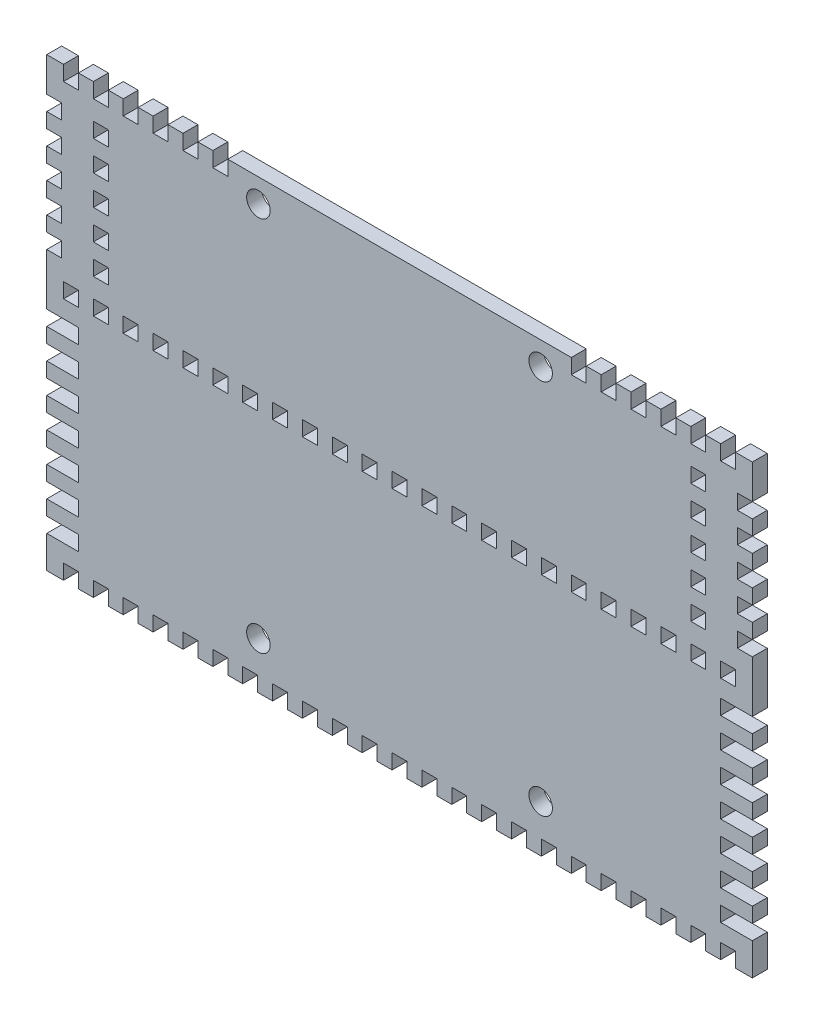
SolidWorks part; units mm, degrees
ref_plane "Front Plane" through (0, 0, 0) normal (0, 0, 1) x (1, 0, 0)
ref_plane "Top Plane" through (0, 0, 0) normal (0, 1, 0) x (1, 0, 0)
ref_plane "Right Plane" through (0, 0, 0) normal (1, 0, 0) x (0, 0, -1)
sketch "Sketch1" plane through (0, 0, 0) normal (0, 0, 1) x (1, 0, 0)
  line L1 (75, -27.5) -> (-75, -27.5)
  line L2 (75, -27.5) -> (75, 27.5)
  line L3 (75, 27.5) -> (-75, 27.5)
  line L4 (-75, -27.5) -> (-75, 27.5)
  line L5 (75, -27.5) -> (-75, 27.5) construction
  line L6 (75, 27.5) -> (-75, -27.5) construction
  point P0 (0, 0)
  dimension "D1" = 150
  dimension "D2" = 55
extrude "Boss-Extrude1" add sketch "Sketch1" along normal blind 3.175
sketch "Sketch2" plane through (0, 0, 0) normal (0, 0, -1) x (-1, 0, 0)
  line L0 (-75, 27.5) -> (75, 27.5) construction
  line L1 (-1.5875, 30.675) -> (1.5875, 30.675)
  line L2 (-1.5875, 30.675) -> (-1.5875, 24.325)
  line L3 (-1.5875, 24.325) -> (1.5875, 24.325)
  line L4 (1.5875, 30.675) -> (1.5875, 24.325)
  line L5 (-1.5875, 30.675) -> (1.5875, 24.325) construction
  line L6 (-1.5875, 24.325) -> (1.5875, 30.675) construction
  point P0 (0, 27.5)
  dimension "D1" = 3.175
  dimension "D2" = 6.35
extrude "Cut-Extrude1" cut sketch "Sketch2" against normal up to next
pattern_linear "LPattern1" count 12 spacing 6.35 along (1, 0, 0) count 12 spacing 6.35 along (-1, 0, 0) of "Cut-Extrude1" pattern seed only yes
mirror "Mirror1" about plane through (0, 0, 0) normal (0, 1, 0) of "LPattern1"
sketch "Sketch3" plane through (0, 0, 0) normal (0, 0, -1) x (-1, 0, 0)
  line L0 (-75, -27.5) -> (-75, 27.5) construction
  line L1 (-78.175, 1.5875) -> (-71.825, 1.5875)
  line L2 (-78.175, 1.5875) -> (-78.175, -1.5875)
  line L3 (-78.175, -1.5875) -> (-71.825, -1.5875)
  line L4 (-71.825, 1.5875) -> (-71.825, -1.5875)
  line L5 (-78.175, 1.5875) -> (-71.825, -1.5875) construction
  line L6 (-78.175, -1.5875) -> (-71.825, 1.5875) construction
  point P0 (-75, 0)
  dimension "D1" = 3.175
  dimension "D2" = 6.35
extrude "Cut-Extrude2" cut sketch "Sketch3" against normal blind 10
pattern_linear "LPattern2" count 4 spacing 6.35 along (0, 1, 0) count 4 spacing 6.35 along (0, -1, 0) of "Cut-Extrude2" pattern seed only yes
mirror "Mirror2" about plane through (0, 0, 0) normal (1, 0, 0) of "LPattern2"
sketch "Sketch4" plane through (0, 0, 0) normal (0, 0, -1) x (-1, 0, 0)
  line L0 (-45, 0) -> (-25, 0) construction
  line L1 (-45, 1.5) -> (-25, 1.5)
  line L2 (-45, -1.5) -> (-25, -1.5)
  line L3 (25, 0) -> (45, 0) construction
  line L4 (25, 1.5) -> (45, 1.5)
  line L5 (25, -1.5) -> (45, -1.5)
  arc A0 (-45, 1.5) -> (-45, -1.5) centre (-45, 0) ccw
  arc A1 (-25, -1.5) -> (-25, 1.5) centre (-25, 0) ccw
  arc A2 (25, 1.5) -> (25, -1.5) centre (25, 0) ccw
  arc A3 (45, -1.5) -> (45, 1.5) centre (45, 0) ccw
  point P2 (-35, 0)
  point P9 (35, 0)
  dimension "D1" = 35
  dimension "D2" = 35
  dimension "D3" = 3
  dimension "D4" = 3
  dimension "D5" = 20
  dimension "D6" = 20
extrude "Cut-Extrude3" [suppressed] cut sketch "Sketch4" against normal blind 10
sketch "Sketch5" plane through (0, 0, 0) normal (0, 0, -1) x (-1, 0, 0)
  line L1 (-75, 27.5) -> (75, 27.5)
  line L2 (-75, 27.5) -> (-75, 67.5)
  line L3 (-75, 67.5) -> (75, 67.5)
  line L4 (75, 27.5) -> (75, 67.5)
  dimension "D1" = 40
extrude "Boss-Extrude2" add sketch "Sketch5" against normal up to surface (3.175 mm away) up to face at (0, 0, 3.175)
sketch "Sketch6" plane through (0, 0, 0) normal (0, 0, -1) x (-1, 0, 0)
  line L0 (-35, 44.0688) -> (35, 44.0688) construction
  line L1 (-25, 44.0687) -> (-45, 44.0687) construction
  line L2 (-25, 42.5688) -> (-45, 42.5688)
  line L3 (-25, 45.5688) -> (-45, 45.5688)
  line L4 (25, 44.0687) -> (45, 44.0688) construction
  line L5 (25, 45.5688) -> (45, 45.5688)
  line L6 (25, 42.5687) -> (45, 42.5688)
  arc A0 (-25, 42.5688) -> (-25, 45.5688) centre (-25, 44.0687) ccw
  arc A1 (-45, 45.5688) -> (-45, 42.5688) centre (-45, 44.0687) ccw
  arc A2 (25, 45.5688) -> (25, 42.5687) centre (25, 44.0687) ccw
  arc A3 (45, 42.5688) -> (45, 45.5688) centre (45, 44.0688) ccw
  point P3 (0, 44.0688)
  point P6 (-35, 44.0688)
  point P12 (35, 44.0688)
  dimension "D1" = 70
  dimension "D2" = 3
  dimension "D3" = 3
  dimension "D4" = 20
  dimension "D5" = 20
extrude "Cut-Extrude4" [suppressed] cut sketch "Sketch6" against normal blind 10
sketch "Sketch7" plane through (0, 0, 0) normal (0, 0, -1) x (-1, 0, 0)
  line L0 (75, 67.5) -> (-75, 67.5) construction
  line L1 (0, 67.5) -> (1.5875, 67.5)
  line L3 (0, 64.325) -> (1.5875, 64.325)
  line L4 (1.5875, 67.5) -> (1.5875, 64.325)
  line L6 (0, 64.325) -> (-1.5875, 64.325)
  line L8 (0, 67.5) -> (-1.5875, 67.5)
  line L9 (-1.5875, 64.325) -> (-1.5875, 67.5)
  dimension "D1" = 1.5875
  dimension "D2" = 3.175
  dimension "D3" = 1.5875
extrude "Cut-Extrude5" cut sketch "Sketch7" against normal blind 10
pattern_linear "LPattern3" count 12 spacing 6.35 along (1, 0, 0) count 12 spacing 6.35 along (-1, 0, 0) of "Cut-Extrude5" pattern seed only yes
sketch "Sketch8" plane through (0, 0, 0) normal (0, 0, -1) x (-1, 0, 0)
  line L0 (-68.2625, 24.325) -> (-68.2625, 27.5) construction
  line L1 (-71.825, 20.6375) -> (-68.2625, 20.6375)
  line L2 (-71.825, 20.6375) -> (-71.825, 17.4625)
  line L3 (-71.825, 17.4625) -> (-68.2625, 17.4625)
  line L4 (-68.2625, 20.6375) -> (-68.2625, 17.4625)
extrude "Cut-Extrude6" cut sketch "Sketch8" against normal blind 10
pattern_linear "LPattern4" count 7 spacing 6.35 along (0, -1, 0) of "Cut-Extrude6"
mirror "Mirror3" about plane through (0, 0, 0) normal (1, 0, 0) of "LPattern4"
sketch "Sketch9" plane through (0, 0, 0) normal (0, 0, -1) x (-1, 0, 0)
  line L1 (-30, 62.5) -> (30, 62.5) construction
  line L2 (-30, 62.5) -> (-30, -17.5) construction
  line L3 (-30, -17.5) -> (30, -17.5) construction
  line L4 (30, 62.5) -> (30, -17.5) construction
  line L5 (-30, 62.5) -> (30, -17.5) construction
  line L6 (-30, -17.5) -> (30, 62.5) construction
  line L7 (-39.6875, -27.5) -> (-42.8625, -27.5) construction
  point P0 (0, 22.5)
  dimension "D1" = 60
  dimension "D2" = 80
  dimension "D3" = 50
sketch "Sketch11" plane through (0, 0, 0) normal (0, 0, -1) x (-1, 0, 0)
  line L1 (-36.5125, 67.5) -> (36.5125, 67.5)
  line L2 (-36.5125, 67.5) -> (-36.5125, 64.325)
  line L3 (-36.5125, 64.325) -> (36.5125, 64.325)
  line L4 (36.5125, 67.5) -> (36.5125, 64.325)
extrude "Boss-Extrude3" add sketch "Sketch11" against normal up to surface (3.175 mm away) up to face at (-19.05, 25.9125, 3.175)
sketch "Sketch10" plane through (0, 0, 0) normal (0, 0, -1) x (-1, 0, 0)
  circle A0 centre (-30, 62.5) radius 2.5
  circle A1 centre (30, 62.5) radius 2.5
  circle A2 centre (30, -17.5) radius 2.5
  circle A3 centre (-30, -17.5) radius 2.5
  dimension "D1" = 5
extrude "Cut-Extrude7" cut sketch "Sketch10" against normal blind 10
sketch "Sketch12" plane through (0, 0, 0) normal (0, 0, -1) x (-1, 0, 0)
  line L0 (-75, 67.5) -> (-75, 24.325) construction
  line L1 (-75, 20.6375) -> (-75, 67.5) construction
  line L3 (-78.175, 47.5) -> (-71.825, 47.5)
  line L4 (-78.175, 47.5) -> (-78.175, 44.325)
  line L5 (-78.175, 44.325) -> (-71.825, 44.325)
  line L6 (-71.825, 47.5) -> (-71.825, 44.325)
  line L7 (-78.175, 47.5) -> (-71.825, 44.325) construction
  line L8 (-78.175, 44.325) -> (-71.825, 47.5) construction
  point P5 (-75, 45.9125)
  dimension "D1" = 3.175
  dimension "D2" = 6.35
extrude "Cut-Extrude8" cut sketch "Sketch12" against normal blind 10
pattern_linear "LPattern5" count 3 spacing 6.35 along (0, 1, 0) count 3 spacing 6.35 along (0, -1, 0) of "Cut-Extrude8" pattern seed only yes
mirror "Mirror4" about plane through (0, 0, 0) normal (1, 0, 0) of "LPattern5"
sketch "Sketch13" plane through (0, 0, 0) normal (0, 0, -1) x (-1, 0, 0)
  line L1 (-65.0875, 47.5) -> (-61.9125, 47.5)
  line L2 (-65.0875, 47.5) -> (-65.0875, 44.325)
  line L3 (-65.0875, 44.325) -> (-61.9125, 44.325)
  line L4 (-61.9125, 47.5) -> (-61.9125, 44.325)
extrude "Cut-Extrude9" cut sketch "Sketch13" against normal blind 10
pattern_linear "LPattern6" count 3 spacing 6.35 along (0, 1, 0) count 3 spacing 6.35 along (0, -1, 0) of "Cut-Extrude9" pattern seed only yes
mirror "Mirror5" about plane through (0, 0, 0) normal (1, 0, 0) of "LPattern6"
